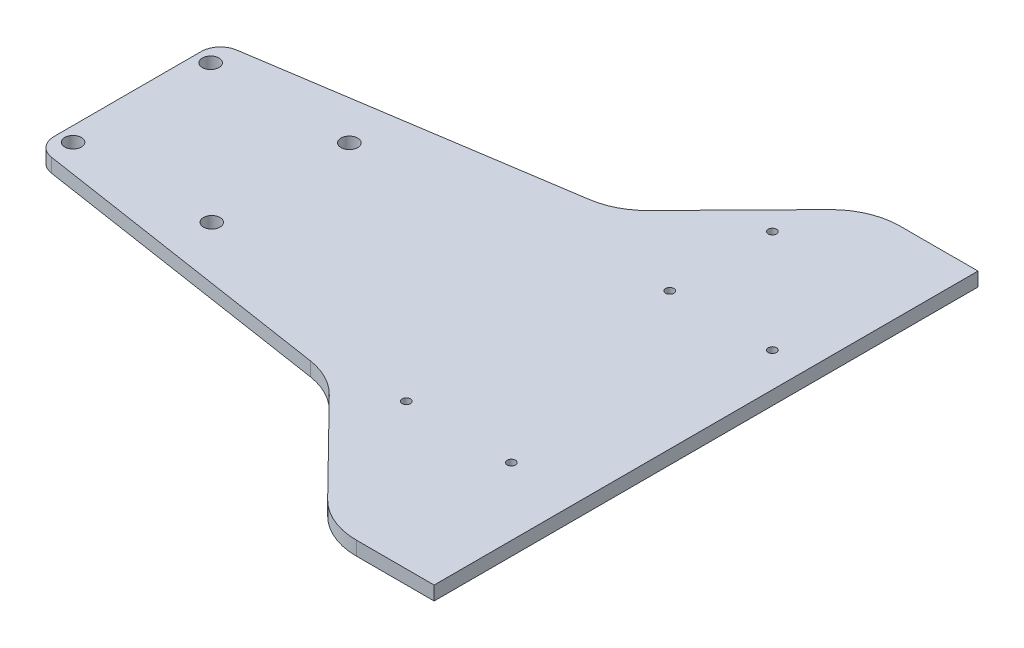
SolidWorks part; units mm, degrees
material "Plastique personnalisé"
ref_plane "Plan de face" through (0, 0, 0) normal (0, 0, 1) x (1, 0, 0)
ref_plane "Plan de dessus" through (0, 0, 0) normal (0, 1, 0) x (1, 0, 0)
ref_plane "Plan de droite" through (0, 0, 0) normal (1, 0, 0) x (0, 0, -1)
sketch "Esquisse1" plane through (0, 0, 0) normal (0, 1, 0) x (1, 0, 0)
  line L0 (0, 0) -> (200, 0) construction
  line L1 (200, -98) -> (200, 98) construction
  line L2 (0, -32.5) -> (0, 32.5) construction
  line L4 (200, 98) -> (180.4869, 98)
  line L5 (162.6514, 90.5184) -> (130.2275, 57.5077)
  line L6 (0, 19.6247) -> (0, -19.6247)
  line L7 (200, 98) -> (200, -98)
  line L8 (200, -98) -> (180.4869, -98)
  line L9 (162.6514, -90.5184) -> (130.2275, -57.5077)
  line L11 (116.1812, -50.3149) -> (0, -32.5)
  line L12 (0, -19.6247) -> (0, -32.5)
  line L13 (116.1812, 50.3149) -> (0, 32.5)
  line L14 (0, 32.5) -> (0, 19.6247)
  arc A0 (116.1812, 50.3149) -> (130.2275, 57.5077) centre (112.392, 75.0261) ccw
  arc A1 (180.4869, 98) -> (162.6514, 90.5184) centre (180.4869, 73) ccw
  arc A3 (180.4869, -98) -> (162.6514, -90.5184) centre (180.4869, -73) cw
  arc A4 (116.1812, -50.3149) -> (130.2275, -57.5077) centre (112.392, -75.0261) cw
  point P13 (170, 98)
  dimension "D5" = 25
  dimension "D1" = 200
  dimension "D2" = 98
  dimension "D3" = 32.5
  dimension "D4" = 30
extrude "Boss.-Extru.1" add sketch "Esquisse1" along normal blind 5
fillet "Congé3" radius 7 2 edges at (0, 2.5, 32.5) (0, 2.5, -32.5)
sketch "Esquisse3" plane through (0, 5, 0) normal (0, 1, 0) x (1, 0, 0)
  circle A0 centre (5.2281, -24.8573) radius 3
  circle A1 centre (5.2281, 24.7436) radius 3
  circle A2 centre (55.2084, -24.8573) radius 3
  circle A3 centre (55.2084, 24.7436) radius 3
  dimension "D1" = 6
  dimension "D2" = 6
  dimension "D3" = 6
  dimension "D4" = 6
extrude "Enlèv. mat.-Extru.1" cut sketch "Esquisse3" against normal blind 5
sketch "Esquisse8" plane through (0, 5, 0) normal (0, 1, 0) x (1, 0, 0)
  circle A0 centre (196.1489, 36.2746) radius 1.5
  circle A2 centre (159.1489, 73.2746) radius 1.5
  circle A3 centre (159.1489, 36.2746) radius 1.5
extrude "Enlèv. mat.-Extru.5" cut sketch "Esquisse8" against normal blind 10
ref_plane "section" through (100, 0, 0) normal (1, 0, 0) x (0, 0, -1)
sketch "Esquisse11" plane through (0, 5, 0) normal (0, 1, 0) x (1, 0, 0)
  circle A0 centre (184.1991, -45.8698) radius 1.5
  circle A1 centre (146.1501, -45.6605) radius 1.5
extrude "Enlèv. mat.-Extru.7" cut sketch "Esquisse11" against normal blind 10
sketch "Esquisse12" plane through (0, 0, 0) normal (0, -1, 0) x (-1, 0, 0)
  line L1 (-200, -98) -> (-208.5132, -98)
  line L2 (-200, -98) -> (-200, 98.0231)
  line L3 (-200, 98.0231) -> (-208.5132, 98.0231)
  line L4 (-208.5132, -98) -> (-208.5132, 98.0231)
extrude "Boss.-Extru.2" add sketch "Esquisse12" against normal blind 5
